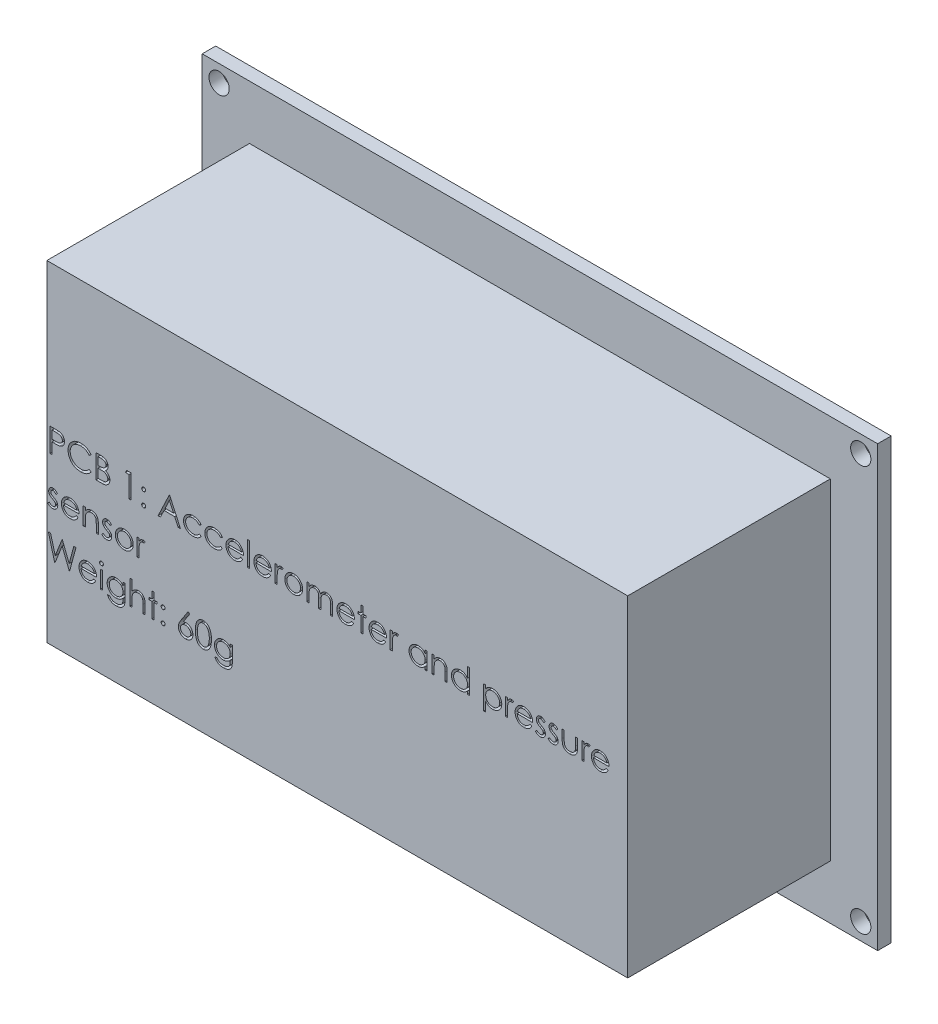
SolidWorks part; units mm, degrees
ref_plane "Front Plane" through (0, 0, 0) normal (0, 0, 1) x (1, 0, 0)
ref_plane "Top Plane" through (0, 0, 0) normal (0, 1, 0) x (1, 0, 0)
ref_plane "Right Plane" through (0, 0, 0) normal (1, 0, 0) x (0, 0, -1)
sketch "Sketch1" plane through (0, 0, 0) normal (0, 0, 1) x (1, 0, 0)
  line L0 (-50, 32.5) -> (50, 32.5)
  line L1 (-50, 32.5) -> (-50, -32.5)
  line L2 (-50, -32.5) -> (50, -32.5)
  line L3 (50, 32.5) -> (50, -32.5)
  line L4 (0, -32.5) -> (0, 32.5) construction
  line L5 (-50, 0) -> (50, 0) construction
  line L6 (-47.5, -30) -> (47.5, -30)
  line L7 (-47.5, -30) -> (-47.5, 30)
  line L8 (-47.5, 30) -> (47.5, 30)
  line L9 (47.5, -30) -> (47.5, 30)
  line L10 (-47.5, -30) -> (47.5, 30) construction
  line L11 (-47.5, 30) -> (47.5, -30) construction
  circle A0 centre (-47.5, 30) radius 1.5
  circle A1 centre (-47.5, -30) radius 1.5
  circle A2 centre (47.5, -30) radius 1.5
  circle A3 centre (47.5, 30) radius 1.5
  point P4 (0, 0)
  point P17 (0, 0)
  dimension "D5" = 3
  dimension "D6" = 3
  dimension "D7" = 3
  dimension "D8" = 3
  dimension "D1" = 65
  dimension "D2" = 100
  dimension "D3" = 2.5
  dimension "D4" = 2.5
extrude "Boss-Extrude1" add sketch "Sketch1" along normal blind 2 contours A3 L8 A0 L7 A1 L6 A2 L9 | L3 L0 L1 L2 A3 L9 A2 L6 A1 L7 A0 L8 region at (0, 31.3073, 0) region at (0, 0, 0)
sketch "Sketch2" plane through (0, 0, 2) normal (0, 0, 1) x (1, 0, 0)
  line L0 (-50, 32.5) -> (50, 32.5) construction
  line L1 (-43, -24.5) -> (43, -24.5)
  line L2 (-43, -24.5) -> (-43, 24.5)
  line L3 (-43, 24.5) -> (43, 24.5)
  line L4 (43, -24.5) -> (43, 24.5)
  line L5 (-43, -24.5) -> (43, 24.5) construction
  line L6 (-43, 24.5) -> (43, -24.5) construction
  line L7 (-50, 32.5) -> (-50, -32.5) construction
  point P0 (0, 0)
  dimension "D1" = 8
  dimension "D2" = 7
extrude "Boss-Extrude2" add sketch "Sketch2" along normal blind 30
sketch "Sketch3" plane through (0, 0, 32) normal (0, 0, 1) x (1, 0, 0)
  line L0 (-43, 0) -> (43, 0) construction
  line L1 (-43, 24.5) -> (-43, -24.5) construction
  line L2 (43, -24.5) -> (43, 24.5) construction
  text T0 "PCB 1: Accelerometer and pressure \r\nsensor\r\nWeight: 60g"
  dimension "D1" = 43
  dimension "D2" = 43
extrude "Cut-Extrude1" cut sketch "Sketch3" against normal blind 2
